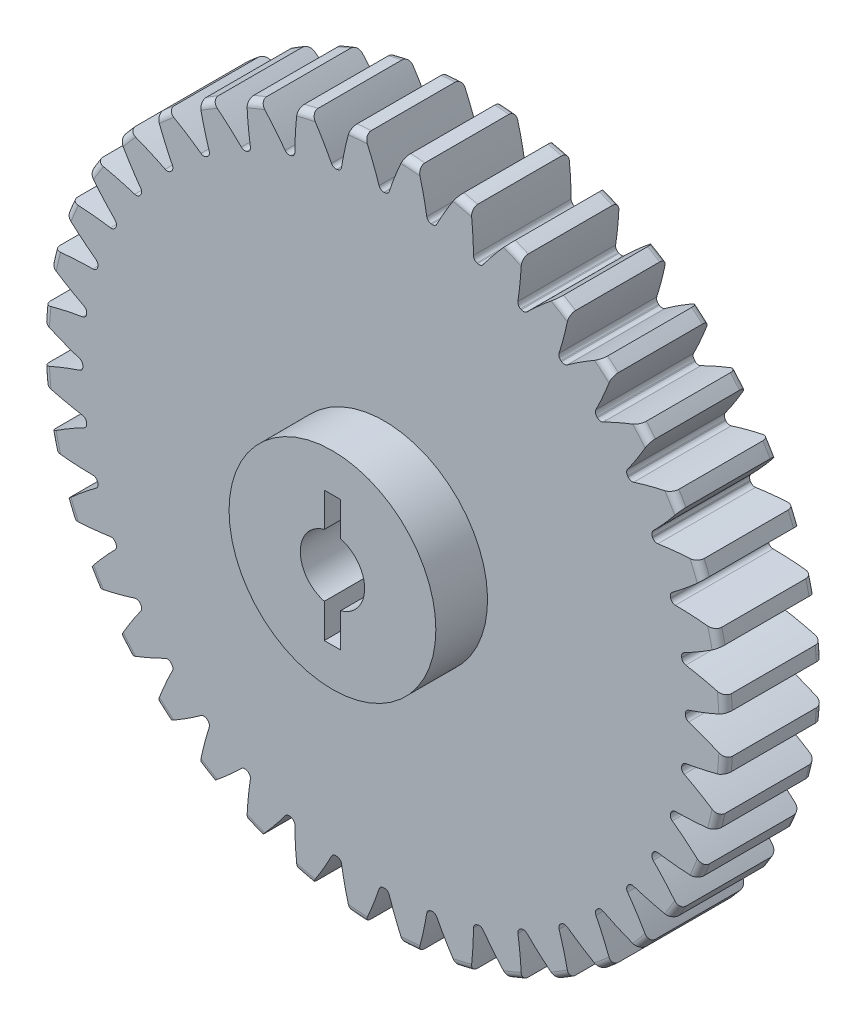
SolidWorks part; units mm, degrees
ref_plane "Front Plane" through (0, 0, 0) normal (0, 0, 1) x (1, 0, 0)
ref_plane "Top Plane" through (0, 0, 0) normal (0, 1, 0) x (1, 0, 0)
ref_plane "Right Plane" through (0, 0, 0) normal (1, 0, 0) x (0, 0, -1)
sketch "Sketch1" plane through (0, 0, 0) normal (0, 0, 1) x (1, 0, 0)
  line L0 (-508, 0) -> (508, 0) construction
  circle A0 centre (0, 0) radius 21 construction
  circle A1 centre (0, 0) radius 20 construction
  circle A2 centre (0, 0) radius 18.5 construction
  circle A3 centre (0, 0) radius 8 construction
  circle A4 centre (0, 0) radius 4 construction
  dimension "D2" = 1
  dimension "D3" = 2.5
  dimension "D1" = 2.5
sketch "Sketch2" plane through (0, 0, 0) normal (1, 0, 0) x (0, 0, -1)
  line L0 (0, 0) -> (-6, 0) construction
  line L1 (-6, 0) -> (-12, 0) construction
  dimension "Overall Width" = 12
  dimension "Face Width" = 6
sketch "Sketch4" plane through (0, 0, 0) normal (1, 0, 0) x (0, 0, -1)
  line L0 (-12, 4) -> (-12, 8)
  line L1 (-12, 8) -> (-6, 8)
  line L2 (-6, 8) -> (-6, 21)
  line L3 (-6, 21) -> (0, 21)
  line L4 (0, 21) -> (0, 4)
  line L5 (-6, 8) -> (-6, 0) construction
  line L6 (0, 21) -> (0, -21) construction
  line L7 (-6, 8) -> (0, 8) construction
  line L12 (-12, 4) -> (0, 4)
revolve "Revolve1" add sketch "Sketch4" angle 360 about L1
fillet "Fillet2" radius 0.42 4 edges at (0, 8, 12) (0, 8, 6) (0, 21, 6) (0, 21, 0)
sketch "Sketch7" plane through (0, 0, 6) normal (0, 0, 1) x (1, 0, 0)
  line L0 (0, 0) -> (0, 21) construction
  line L1 (0.7852, 19.9846) -> (1.1869, 20.9664) construction
  line L3 (1.6476, 20.9353) -> (1.5692, 19.9383) construction
  line L4 (1.5692, 19.9383) -> (1.4515, 18.443) construction
  line L5 (0, 0) -> (1.4515, 18.443) construction
  line L6 (0.7852, 19.9846) -> (0, 0) construction
  line L7 (0.7852, 19.9846) -> (0.8245, 20.9838) construction
  line L8 (0.7852, 19.9846) -> (0, 0) construction
  circle A0 centre (0, 0) radius 21 construction
  arc A1 (-0.027, 18.5) -> (0.027, 18.5) centre (0, 0) cw
  circle A2 centre (0, 0) radius 18.5 construction
  arc A3 (-0.7852, 19.9846) -> (0.7852, 19.9846) centre (0, 0) cw construction
  circle A4 centre (0, 0) radius 20 construction
  arc A5 (2.0774, 20.897) -> (1.2172, 20.9647) centre (0, 0) ccw construction
  arc A6 (0.7852, 19.9846) -> (2.3507, 19.8614) centre (0, 0) cw construction
  arc A7 (-1.2172, 20.9647) -> (1.2172, 20.9647) centre (0, 0) cw
  arc A8 (0.3122, 18.7056) -> (1.2172, 20.9647) centre (19.296, 12.4116) cw
  arc A9 (-0.3122, 18.7056) -> (-1.2172, 20.9647) centre (-19.296, 12.4116) ccw
  arc A10 (-0.027, 18.5) -> (-0.3122, 18.7056) centre (-0.0274, 18.8) cw
  arc A11 (0.027, 18.5) -> (0.3122, 18.7056) centre (0.0274, 18.8) ccw
  point P26 (-0.2447, 18.4984)
  point P29 (0.2447, 18.4984)
  dimension "D4" = 0.3
  dimension "D5" = 20
  dimension "D3" = 20
  dimension "D1" = 3.1416
  dimension "D2" = 1.5708
extrude "Cut-Extrude2" cut sketch "Sketch7" against normal through all
pattern_circular "CirPattern1" count 40 over 360 about axis through (0, 0, 12) along (0, 0, -1) of "Cut-Extrude2"
sketch "Sketch8" plane through (0, 0, 0) normal (0, 0, -1) x (-1, 0, 0)
  circle A0 centre (0, 0) radius 2
  circle A1 centre (0, 0) radius 4
  circle A2 centre (0, 0) radius 4 construction
  dimension "D1" = 4
extrude "Boss-Extrude1" add sketch "Sketch8" against normal up to surface (12 mm away) up to face at (0, -7.58, 12)
sketch "Sketch9" plane through (0, 0, 12) normal (0, 0, 1) x (1, 0, 0)
  circle A0 centre (0, 0) radius 8.42
  dimension "D1" = 16.84
extrude "Cut-Extrude3" cut sketch "Sketch9" against normal up to surface (6 mm away) up to face at (0, 0, 6)
ref_plane "Plane1" through (0, 0, 3) normal (0, 0, 1) x (1, 0, 0)
sketch "Sketch10" plane through (0, 0, 3) normal (0, 0, 1) x (1, 0, 0)
  circle A0 centre (0, 0) radius 1.975
  circle A1 centre (0, 0) radius 6.35
  dimension "D1" = 3.95
  dimension "D2" = 12.7
extrude "Boss-Extrude2" add sketch "Sketch10" along normal mid plane 12.35
sketch "Sketch12" plane through (0, 0, 9.175) normal (0, 0, 1) x (1, 0, 0)
  line L0 (-0.5, 0) -> (0.5, 0) construction
  line L1 (0.5, 4) -> (0.5, -4)
  line L2 (0.5, 4) -> (-0.5, 4)
  line L3 (-0.5, 4) -> (-0.5, -4)
  line L4 (-0.5, -4) -> (0.5, -4)
  point P4 (0.5, 0)
  point P5 (0, 0)
  dimension "D1" = 1
  dimension "D2" = 8
extrude "Cut-Extrude4" cut sketch "Sketch12" against normal through all
equation "\"D1@Sketch1\"=2.5*(\"Pitch Dia.@Sketch1\"/\"Number of Teeth@Sketch1\")"
equation "\"D1@CirPattern1\"=\"Number of Teeth@Sketch1\""
equation "\"D1@Fillet2\"=\"OD@Sketch1\"*.01"
equation "\"D1@Sketch7\"=3.14159*(\"Pitch Dia.@Sketch1\"/\"Number of Teeth@Sketch1\")"
equation "\"D2@Sketch7\"=\"D1@Sketch7\"/2"
equation "\"D4@Sketch7\"=\"D1@Sketch7\"*.0955"
equation "\"D5@Sketch7\"=\"Pitch Dia.@Sketch1\"/2"
